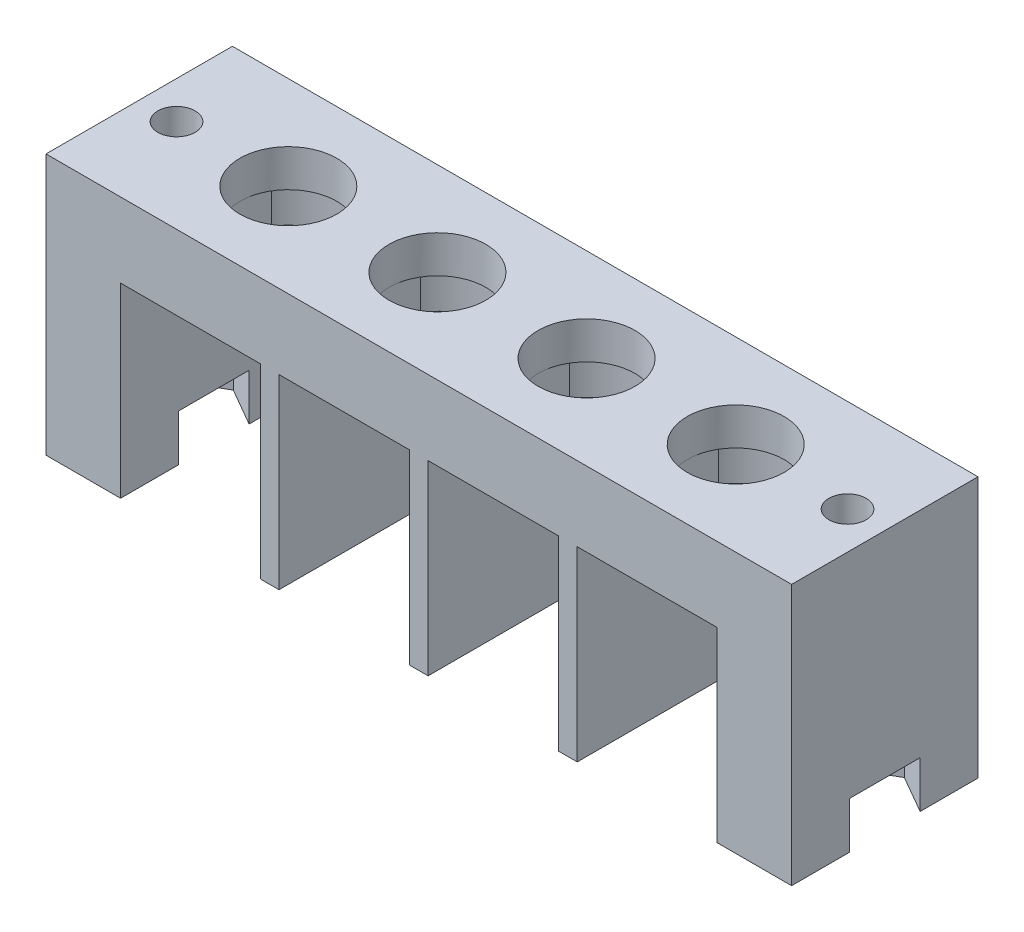
SolidWorks part; units mm, degrees
ref_plane "Płaszczyzna przednia" through (0, 0, 0) normal (0, 0, 1) x (1, 0, 0)
ref_plane "Płaszczyzna górna" through (0, 0, 0) normal (0, 1, 0) x (1, 0, 0)
ref_plane "Płaszczyzna prawa" through (0, 0, 0) normal (1, 0, 0) x (0, 0, -1)
sketch "Sketch1" plane through (0, 0, 0) normal (0, 1, 0) x (1, 0, 0)
  line L1 (-25, -7.3826) -> (15, -7.3826)
  line L2 (-25, -7.3826) -> (-25, 2.6174)
  line L3 (-25, 2.6174) -> (15, 2.6174)
  line L4 (15, -7.3826) -> (15, 2.6174)
  dimension "D1" = 40
  dimension "D2" = 10
extrude "Boss-Extrude1" add sketch "Sketch1" along normal blind 4
sketch "Sketch2" plane through (0, 4, 0) normal (0, 1, 0) x (1, 0, 0)
  line L0 (-25, -2.3826) -> (15, -2.3826) construction
  line L1 (-25, 2.6174) -> (-25, -7.3826) construction
  line L2 (15, -7.3826) -> (15, 2.6174) construction
  line L3 (15, -2.3826) -> (7, -2.3826) construction
  line L4 (7, -2.3826) -> (-1, -2.3826) construction
  line L5 (-1, -2.3826) -> (-9, -2.3826) construction
  line L6 (-9, -2.3826) -> (-17, -2.3826) construction
  circle A0 centre (-17, -2.3826) radius 2.6
  circle A1 centre (-9, -2.3826) radius 2.6
  circle A2 centre (-1, -2.3826) radius 2.6
  circle A3 centre (7, -2.3826) radius 2.6
  dimension "D1" = 8
  dimension "D2" = 8
  dimension "D3" = 8
  dimension "D4" = 8
extrude "Cut-Extrude1" cut sketch "Sketch2" against normal blind 10
sketch "Sketch3" plane through (0, 0, 0) normal (0, -1, 0) x (1, 0, 0)
  line L0 (-19.6, 4.0707) -> (-19.6, 0.6944)
  line L2 (-11.6, 4.0707) -> (-11.6, 0.6944)
  line L4 (-3.6, 4.0707) -> (-3.6, 0.6944)
  line L6 (4.4, 4.0707) -> (4.4, 0.6944)
  arc A0 (-19.6, 0.6944) -> (-19.6, 4.0707) centre (-17, 2.3826) ccw
  arc A1 (-11.6, 0.6944) -> (-11.6, 4.0707) centre (-9, 2.3826) ccw
  arc A2 (-3.6, 0.6944) -> (-3.6, 4.0707) centre (-1, 2.3826) ccw
  arc A3 (4.4, 0.6944) -> (4.4, 4.0707) centre (7, 2.3826) ccw
extrude "Cut-Extrude4" cut sketch "Sketch3" against normal blind 2
sketch "Sketch5" plane through (0, 0, 0) normal (0, -1, 0) x (1, 0, 0)
  line L0 (15, 7.3826) -> (15, -2.6174) construction
  line L5 (-25, -2.6174) -> (15, -2.6174)
  line L10 (-25, -2.6174) -> (-25, -1.6174)
  line L17 (-21, -1.6174) -> (-13.5, -1.6174)
  line L50 (15, -2.6174) -> (15, -1.6174)
  line L59 (-25, 2.8826) -> (-13.5, 2.8826) construction
  line L60 (-25, 7.3826) -> (-21, 7.3826)
  line L61 (-25, 7.3826) -> (-25, -1.6174)
  line L63 (-21, 7.3826) -> (-21, -1.6174)
  line L64 (15, 7.3826) -> (11, 7.3826)
  line L65 (15, 7.3826) -> (15, -1.6174)
  line L67 (11, 7.3826) -> (11, -1.6174)
  line L68 (-13.5, 2.8826) -> (-13.5, 7.3826) construction
  line L69 (-25, 7.3826) -> (15, 7.3826) construction
  line L70 (-13.5, 7.3826) -> (-13.5, -1.6174) construction
  line L71 (-13.5, 2.8826) -> (-5.5, 2.8826) construction
  line L72 (-5.5, 2.8826) -> (-5.5, 7.3826) construction
  line L73 (-5.5, 7.3826) -> (-5.5, -1.6174) construction
  line L74 (-5.5, 2.8826) -> (2.5, 2.8826) construction
  line L75 (2.5, 2.8826) -> (2.5, 7.3826) construction
  line L76 (2.5, 7.3826) -> (2.5, -1.6174) construction
  line L77 (-12.5, -1.6174) -> (-5.5, -1.6174)
  line L79 (-13.5, -1.6174) -> (-13.5, 7.3826)
  line L80 (-13.5, 7.3826) -> (-12.5, 7.3826)
  line L81 (-12.5, -1.6174) -> (-12.5, 7.3826)
  line L83 (-5.5, -1.6174) -> (-5.5, 7.3826)
  line L84 (-5.5, 7.3826) -> (-4.5, 7.3826)
  line L85 (-4.5, -1.6174) -> (-4.5, 7.3826)
  line L87 (2.5, -1.6174) -> (2.5, 7.3826)
  line L88 (2.5, 7.3826) -> (3.5, 7.3826)
  line L89 (3.5, -1.6174) -> (3.5, 7.3826)
  line L90 (-4.5, -1.6174) -> (2.5, -1.6174)
  line L91 (3.5, -1.6174) -> (11, -1.6174)
  line M18 (15, 7.3826) -> (-25, 7.3826)
  line M23 (-25, 7.3826) -> (-25, -2.6174)
  line M24 (-25, -2.6174) -> (15, -2.6174)
  line M25 (15, -2.6174) -> (15, 7.3826)
  dimension "D1" = 1
  dimension "D2" = 4
  dimension "D3" = 4
  dimension "D4" = 1
  dimension "D5" = 1
  dimension "D6" = 1
extrude "Boss-Extrude4" add sketch "Sketch5" along normal blind 10 contours L90 L85 M18 M23 M24 M25 region at (-5, 0, 1.4437)
sketch "Sketch6" plane through (0, -10, 0) normal (0, -1, 0) x (1, 0, 0)
  line L0 (-23, 7.3826) -> (-23, -2.6174) construction
  line L1 (-21, 7.3826) -> (-25, 7.3826) construction
  line L2 (-25, -2.6174) -> (15, -2.6174) construction
  line L3 (-23, -2.6174) -> (-23, 2.3826) construction
  line L4 (-23, 2.3826) -> (-25, 2.3826) construction
  line L5 (-25, 7.3826) -> (-25, -2.6174) construction
  line L6 (13, 7.3826) -> (13, -2.6174) construction
  line L7 (15, 7.3826) -> (11, 7.3826) construction
  circle A0 centre (-23, 2.3826) radius 1
  circle A1 centre (13, 2.3826) radius 1
extrude "Cut-Extrude5" cut sketch "Sketch6" against normal blind 40
sketch "Sketch8" plane through (0, -10, 0) normal (0, -1, 0) x (1, 0, 0)
  line L1 (13, 5.4326) -> (10.3586, 3.9076)
  line L2 (10.3586, 3.9076) -> (10.3586, 0.8576)
  line L3 (10.3586, 0.8576) -> (13, -0.6674)
  line L4 (13, -0.6674) -> (15.6414, 0.8576)
  line L5 (15.6414, 0.8576) -> (15.6414, 3.9076)
  line L6 (15.6414, 3.9076) -> (13, 5.4326)
  line L7 (-23, 5.4326) -> (-25.6414, 3.9076)
  line L8 (-25.6414, 3.9076) -> (-25.6414, 0.8576)
  line L9 (-25.6414, 0.8576) -> (-23, -0.6674)
  line L10 (-23, -0.6674) -> (-20.3586, 0.8576)
  line L11 (-20.3586, 0.8576) -> (-20.3586, 3.9076)
  line L12 (-20.3586, 3.9076) -> (-23, 5.4326)
  circle A0 centre (13, 2.3826) radius 3.05 construction
  circle A1 centre (-23, 2.3826) radius 2.6414 construction
extrude "Cut-Extrude6" cut sketch "Sketch8" against normal blind 2.5
